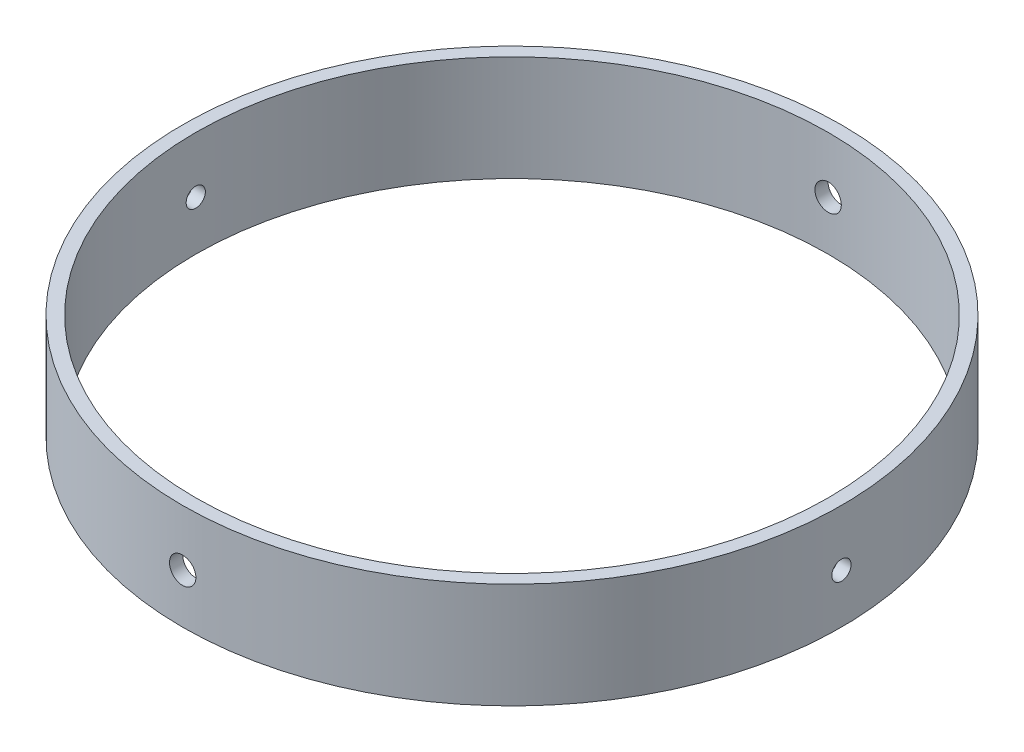
SolidWorks part; units mm, degrees
ref_plane "Front Plane" through (0, 0, 0) normal (0, 0, 1) x (1, 0, 0)
ref_plane "Top Plane" through (0, 0, 0) normal (0, 1, 0) x (1, 0, 0)
ref_plane "Right Plane" through (0, 0, 0) normal (1, 0, 0) x (0, 0, -1)
sketch "Sketch1" plane through (0, 0, 0) normal (0, 1, 0) x (1, 0, 0)
  circle A0 centre (0, 0) radius 79.375
  circle A1 centre (0, 0) radius 76.2
  dimension "D1" = 158.75
  dimension "D2" = 152.4
extrude "Boss-Extrude1" add sketch "Sketch1" along normal blind 25.4
ref_plane "Plane1" through (0, 0, 79.375) normal (0, 0, 1) x (1, 0, 0)
sketch "Sketch2" plane through (0, 0, 79.375) normal (0, 0, 1) x (1, 0, 0)
  circle A0 centre (0, 11.8909) radius 2.3114
  dimension "D1" = 4.6228
ref_axis "Axis1" through (0, 25.4, 0) along (0, -1, 0)
extrude "Cut-Extrude4" cut sketch "Sketch2" against normal up to next
pattern_circular "CirPattern1" count 4 over 360 about axis through (0, 25.4, 0) along (0, -1, 0) of "Cut-Extrude4"
ref_axis "Axis2" through (0, 11.8909, 76.0346) along (0, 0, 1)
ref_axis "Axis3" through (-76.0346, 11.8909, 0) along (-1, 0, 0)
ref_plane "Plane2" through (-76.2, 0, 0) normal (1, 0, 0) x (0, 0, -1)
sketch "Sketch4" plane through (0, 0, 79.375) normal (0, 0, 1) x (1, 0, 0)
  circle A0 centre (0, 11.8909) radius 3.175
  dimension "D1" = 6.35
extrude "Cut-Extrude6" cut sketch "Sketch4" against normal through all both and the other way through all
